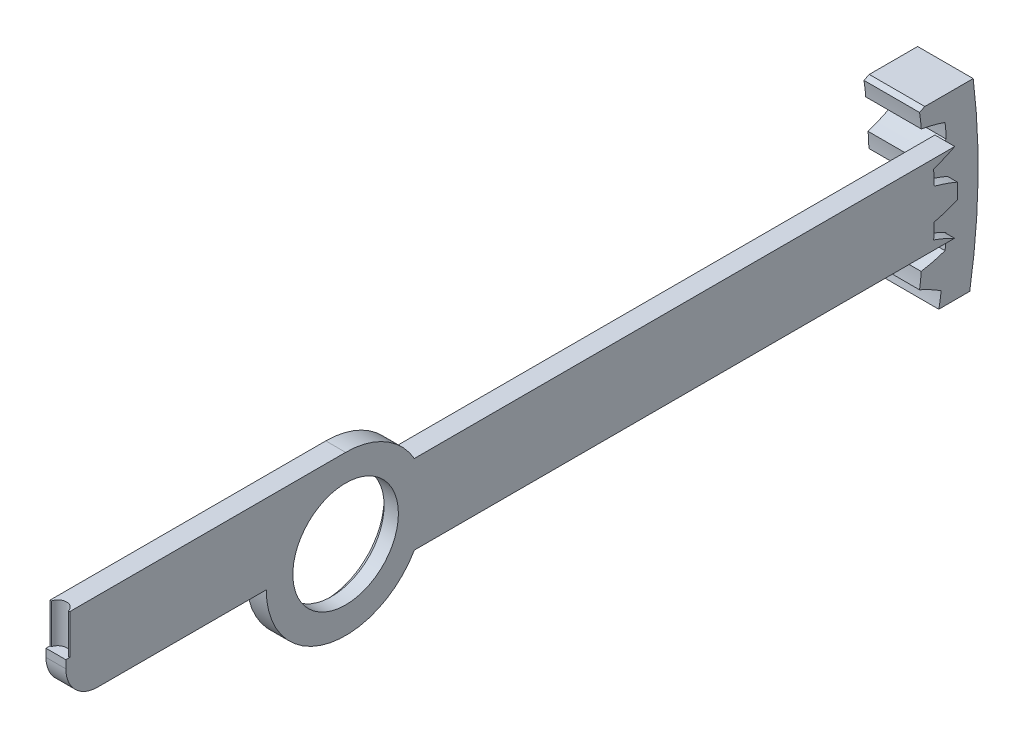
SolidWorks part; units mm, degrees
note: The reader was unsure of these and kept them because the rebuilt part matched: shared geometry of "Эскиз1<5>".
ref_plane "Спереди" through (0, 0, 0) normal (0, 0, 1) x (1, 0, 0)
ref_plane "Сверху" through (0, 0, 0) normal (0, 1, 0) x (1, 0, 0)
ref_plane "Справа" through (0, 0, 0) normal (1, 0, 0) x (0, 0, -1)
sketch "Эскиз1" plane through (0, 0, 0) normal (1, 0, 0) x (0, 0, -1)
  line L0 (-35, 10) -> (-35, 5) construction
  line L1 (-10, 0) -> (-31.25, 0)
  line L2 (0.0037, -0.0135) -> (70.0037, -0.0135) construction
  line L3 (0, 10) -> (-34.75, 10)
  line L4 (-40, 0) -> (-40, 10) construction
  line L5 (-35, 5) -> (-40, 5) construction
  line L6 (0, 0) -> (70, 0) construction
  line L7 (0, -10) -> (0, -13) construction
  line L8 (-35.25, 0) -> (-40, 0) construction
  line L9 (-35.25, 10) -> (-35.25, 5) construction
  line L10 (-35.25, 5) -> (-34.75, 5)
  line L11 (-34.75, 10) -> (-34.75, 5)
  line L12 (-35.25, 10) -> (-34.75, 5) construction
  line L13 (-35.25, 5) -> (-34.75, 10) construction
  line L14 (-35.25, 5) -> (-35.25, 4)
  line L15 (-40, 10) -> (-35.25, 10) construction
  line L16 (-34.3226, 0.016) -> (0.6774, 0.016) construction
  line L17 (0, 0) -> (76.8726, 6.0439) construction
  line L18 (0, 0) -> (57.9572, 4.5164) construction
  line L19 (0, 0) -> (58.1329, -0.0448) construction
  line L20 (0, 0) -> (57.4478, 2.1074) construction
  line L21 (0, 0) -> (57.4361, -2.4064) construction
  line L22 (0, 10) -> (74.2272, 10) construction
  line L23 (0, -13) -> (79.8912, -13) construction
  line L24 (0, 0) -> (57.0702, -6.9053) construction
  line L25 (73.5593, 9.6858) -> (74.2272, 10)
  line L26 (74.2272, 10) -> (80.3219, 10)
  line L27 (4.3843, -5) -> (76.7218, -5) construction
  line L28 (76.7218, -5) -> (8.6603, -5)
  line L29 (76.7218, 5) -> (8.6603, 5)
  line L30 (0, 0) -> (0, -5) construction
  line L31 (0, -5) -> (4.3843, -5) construction
  line L32 (76.7218, 5) -> (76.7504, 5)
  line L33 (8.6603, 5) -> (8.6594, 5)
  line L34 (0, 0) -> (56.3525, -11.3617) construction
  line L35 (79.8912, -13) -> (75.9886, -13.007)
  circle A0 centre (0, 0) radius 10
  circle A1 centre (0, 0) radius 6.65
  arc A2 (76.772, 6.9924) -> (73.7841, 7.7696) centre (70.0232, -12.82) ccw
  arc A3 (74.0739, 3.8687) -> (76.9255, 5.0916) centre (68.0418, 21.8713) ccw
  arc A4 (-35.25, 4) -> (-31.25, 0) centre (-31.25, 4) ccw
  arc A5 (76.772, 6.9924) -> (76.9255, 5.0916) centre (57.9572, 4.5164) cw
  arc A6 (77.0839, 0.9474) -> (74.1663, 1.9566) centre (68.8015, -18.2744) ccw
  arc A7 (77.0839, 0.9474) -> (77.0878, -0.9596) centre (58.1329, -0.0448) cw
  arc A8 (74.1491, -1.955) -> (77.0878, -0.9596) centre (69.5481, 16.4653) ccw
  arc A9 (76.9206, -5.1035) -> (74.0912, -3.8685) centre (67.1556, -23.6162) ccw
  arc A10 (76.9206, -5.1035) -> (76.7749, -7.0049) centre (57.9502, -4.6057) cw
  arc A11 (73.7672, -7.7666) -> (76.7749, -7.0049) centre (70.6256, 10.9579) ccw
  arc A12 (74.0739, 3.8687) -> (74.1663, 1.9566) centre (57.4478, 2.1074) cw
  arc A13 (74.1491, -1.955) -> (74.0912, -3.8685) centre (57.4361, -2.4064) cw
  arc A14 (73.7672, -7.7666) -> (73.5593, -9.6697) centre (57.0702, -6.9053) cw
  arc A15 (73.7841, 7.7696) -> (73.5593, 9.6858) centre (50.0534, 5.9559) ccw
  arc A17 (76.2831, -11.1229) -> (75.9886, -13.007) centre (57.4102, -9.1382) cw
  arc A19 (76.2831, -11.1229) -> (73.5593, -9.6697) centre (65.0957, -28.8124) ccw
  arc A20 (79.8912, -13) -> (80.3219, 10) centre (0, 0) ccw
  arc A21 (72.9304, -13.5304) -> (75.9886, -13.007) centre (71.2676, 5.3829) ccw [skipped]
  arc A22 (72.9304, -13.5304) -> (72.5738, -15.4112) centre (56.3525, -11.3617) cw [skipped]
  point P16 (-35, 7.5)
  dimension "D1" = 20
  dimension "D2" = 13.3
  dimension "D7" = 4.5
  dimension "D8" = 4.5
  dimension "D13" = 4
  dimension "D3" = 40
  dimension "D4" = 10
  dimension "D5" = 70
  dimension "D6" = 70
  dimension "D9" = 5
  dimension "D10" = 0.25
  dimension "D11" = 5
  dimension "D12" = 3
  dimension "D14" = 35
  dimension "D16" = 3
  dimension "D19" = 5
  dimension "D15" = 3
  dimension "D17" = 4.5
extrude "Бобышка-Вытянуть1" add sketch "Эскиз1" along normal mid plane 2.5
extrude "Бобышка-Вытянуть2" add sketch "Эскиз1<5>" against normal blind 7
sketch "Эскиз1<5>" plane through (0, 0, 0) normal (1, 0, 0) x (0, 0, -1) same geometry as "Эскиз1"
sketch "Эскиз3" plane through (0, 10, 0) normal (0, 1, 0) x (1, 0, 0)
  line L0 (-1.25, -35) -> (1.25, -35) construction
  line L1 (-1.25, -35.25) -> (-1.25, -34.75) construction
  line L2 (1.25, -35.25) -> (1.25, -34.75) construction
  circle A0 centre (0, -35) radius 1.1
  dimension "D1" = 2.2
extrude "Вырез-Вытянуть1" cut sketch "Эскиз3" against normal blind 5
chamfer "Фаска1" distance 0.7 angle 45 1 edges at (-1.25, 0, -6.65)
